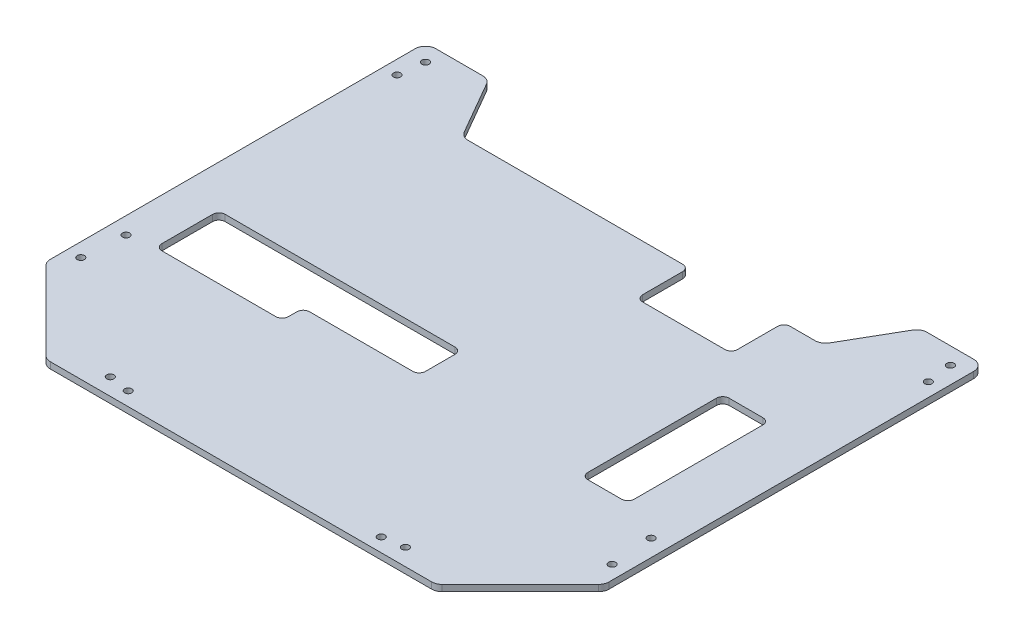
SolidWorks part; units mm, degrees
material "Acier non allié"
ref_plane "Front" through (0, 0, 0) normal (0, 0, 1) x (1, 0, 0)
ref_plane "Top" through (0, 0, 0) normal (0, 1, 0) x (1, 0, 0)
ref_plane "Right" through (0, 0, 0) normal (1, 0, 0) x (0, 0, -1)
sketch "Esquisse1" plane through (0, 0, 0) normal (0, 1, 0) x (1, 0, 0)
  line L0 (0, 0) -> (0, 1919.0564) construction
  line L1 (-92.5, 0) -> (92.5, 0)
  line L2 (92.5, 0) -> (132.5, 40)
  line L3 (132.5, 40) -> (132.5, 220)
  line L4 (132.5, 220) -> (102.5, 220)
  line L5 (102.5, 220) -> (85.1795, 190)
  line L6 (85.1795, 190) -> (-85.1795, 190)
  line L7 (-102.5, 220) -> (-85.1795, 190)
  line L8 (-132.5, 220) -> (-102.5, 220)
  line L9 (-132.5, 40) -> (-132.5, 220)
  line L10 (-92.5, 0) -> (-132.5, 40)
  point P12 (0, 190)
  dimension "D1" = 132.5
  dimension "D2" = 220
  dimension "D3" = 30
  dimension "D4" = 30
  dimension "D5" = 40
  dimension "D6" = 40
  dimension "D7" = 60
extrude "Boss.-Extru.1" add sketch "Esquisse1" along normal blind 3
fillet "Congé1" radius 5 10 edges at (132.5, 1.5, -220) (102.5, 1.5, -220) (85.1795, 1.5, -190) (-85.1795, 1.5, -190) (-102.5, 1.5, -220) (-132.5, 1.5, -220) (-132.5, 1.5, -40) (-92.5, 1.5, 0) (92.5, 1.5, 0) (132.5, 1.5, -40)
sketch "Esquisse2" plane through (0, 0, 0) normal (0, -1, 0) x (1, 0, 0)
  line L0 (0, 0) -> (0, -330.9968) construction
  line L1 (-90.4289, 0) -> (90.4289, 0) construction
  line L2 (-105.3868, -220) -> (-127.5, -220) construction
  line L3 (-132.5, -215) -> (-132.5, -42.0711) construction
  line L4 (-90.4289, 0) -> (90.4289, 0) construction
  line L5 (132.5, -42.0711) -> (132.5, -215) construction
  line L6 (127.5, -220) -> (105.3868, -220) construction
  circle A0 centre (-70, -8) radius 1
  circle A1 centre (-124.5, -70) radius 1
  circle A2 centre (-124.5, -212) radius 1
  circle A3 centre (124.5, -212) radius 1
  circle A4 centre (124.5, -70) radius 1
  circle A5 centre (70, -8) radius 1
  circle A6 centre (126, -50) radius 1.5
  circle A7 centre (126, -200) radius 1.5
  circle A8 centre (-60, -6.5) radius 1.5
  circle A9 centre (60, -6.5) radius 1.5
  circle A10 centre (-126, -50) radius 1.5
  circle A11 centre (-126, -200) radius 1.5
  dimension "D3" = 2
  dimension "D6" = 2
  dimension "D9" = 2
  dimension "D12" = 3
  dimension "D15" = 3
  dimension "D16" = 3
  dimension "D17" = 3
  dimension "D24" = 3
  dimension "D27" = 3
  dimension "D1" = 70
  dimension "D2" = 8
  dimension "D4" = 124.5
  dimension "D5" = 70
  dimension "D7" = 8
  dimension "D8" = 8
  dimension "D10" = 50
  dimension "D11" = 6.5
  dimension "D13" = 20
  dimension "D14" = 6.5
  dimension "D18" = 10
  dimension "D19" = 6.5
  dimension "D20" = 6.5
  dimension "D21" = 10
  dimension "D22" = 50
  dimension "D23" = 6.5
  dimension "D25" = 20
  dimension "D26" = 6.5
extrude "Enlèv. mat.-Extru.1" cut sketch "Esquisse2" against normal through all
hole_wizard "Dégagement M31" positions "Esquisse3" profile "Esquisse4" hole size "M3" standard "ISO" end condition through all
sketch "Esquisse3" plane through (0, 0, 0) normal (0, -1, 0) x (-1, 0, 0)
  point P0 (-70, 8)
  point P3 (-124.5, 70)
  point P6 (-124.5, 212)
  point P9 (124.5, 212)
  point P12 (124.5, 70)
  point P15 (70, 8)
  point P18 (-126, 200)
  point P21 (-126, 50)
  point P24 (-60, 6.5)
  point P27 (60, 6.5)
  point P41 (126, 200)
  point P44 (126, 50)
  point P47 (126, 200)
sketch "Esquisse4" plane through (70, 0, -8) normal (1, 0, 0) x (0, 0, -1)
  line L0 (0, 0) -> (0, 3)
  line L1 (0, 3) -> (1.7, 3)
  line L2 (1.7, 3) -> (1.7, 0)
  line L5 (1.7, 0) -> (0, 0)
  line L11 (0, -6.35) -> (0, 107.95) construction
  dimension "Diamètre du perçage jusqu'au prochain" = 3.4
  dimension "Profondeur du perçage jusqu'au prochain" = 3
sketch "Esquisse5" plane through (0, 0, 0) normal (0, -1, 0) x (1, 0, 0)
  line L6 (82.2927, -190) -> (-82.2927, -190) construction
  line L7 (22.5, -190) -> (67.5, -190)
  line L20 (22.5, -190) -> (22.5, -165)
  line L21 (22.5, -165) -> (67.5, -165)
  line L22 (67.5, -190) -> (67.5, -165)
  line L23 (132.5, -42.0711) -> (132.5, -215) construction
  line L24 (-112.5, -82) -> (-112.5, -72)
  line L25 (-112.5, -102) -> (2.5, -102)
  line L26 (-112.5, -102) -> (-112.5, -82)
  line L27 (-52.5, -82) -> (2.5, -82)
  line L28 (2.5, -102) -> (2.5, -82)
  line L29 (-132.5, -215) -> (-132.5, -42.0711) construction
  line L30 (127.5, -220) -> (105.3868, -220) construction
  line L31 (82.5, -146) -> (104.5, -146)
  line L32 (82.5, -146) -> (82.5, -79)
  line L33 (82.5, -79) -> (104.5, -79)
  line L34 (104.5, -146) -> (104.5, -79)
  line L35 (-90.4289, 0) -> (90.4289, 0) construction
  line L36 (-112.5, -72) -> (-52.5, -72)
  line L37 (-52.5, -82) -> (-52.5, -72)
  dimension "D1" = 65
  dimension "D2" = 110
  dimension "D3" = 25
  dimension "D4" = 82
  dimension "D5" = 135
  dimension "D6" = 20
  dimension "D7" = 115
  dimension "D8" = 50
  dimension "D9" = 74
  dimension "D10" = 67
  dimension "D11" = 22
  dimension "D15" = 30
  dimension "D16" = 60
extrude "Enlèv. mat.-Extru.2" cut sketch "Esquisse5" against normal through all
fillet "Congé2" radius 3 14 edges at (67.5, 1.5, -190) (67.5, 1.5, -165) (22.5, 1.5, -165) (22.5, 1.5, -190) (104.5, 1.5, -146) (82.5, 1.5, -146) (82.5, 1.5, -79) (104.5, 1.5, -79) (2.5, 1.5, -82) (2.5, 1.5, -102) (-112.5, 1.5, -102) (-52.5, 1.5, -72) (-52.5, 1.5, -82) (-112.5, 1.5, -72)
equation "\"WIDTH\"= 300mm'Total width of the robot"
equation "\"LENGTH\"= 220mm'Total length of the robot"
equation "\"CUT_DEPTH\"= 45mm'Depth of the cut on the edges of the plate"
equation "\"Plate_th\"= 3mm'Thickness of the plate"
equation "\"D1\"= \"Plate_th\""
